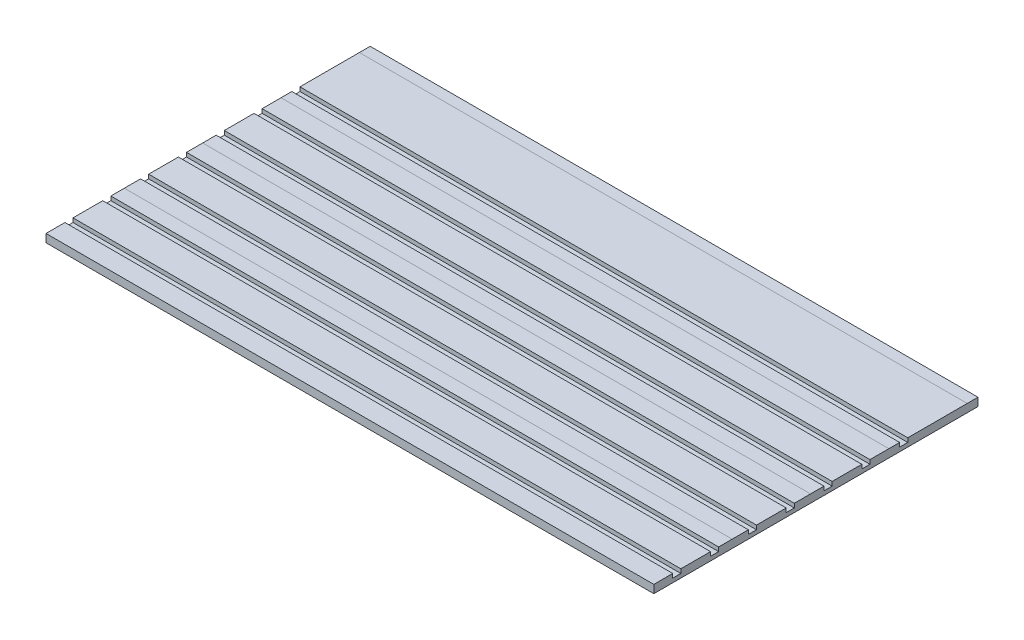
SolidWorks part; units mm, degrees
material "Maple"
ref_plane "Front Plane" through (0, 0, 0) normal (0, 0, 1) x (1, 0, 0)
ref_plane "Top Plane" through (0, 0, 0) normal (0, 1, 0) x (1, 0, 0)
ref_plane "Right Plane" through (0, 0, 0) normal (1, 0, 0) x (0, 0, -1)
sketch "Sketch1" plane through (0, 0, 0) normal (0, 1, 0) x (1, 0, 0)
  line L0 (-714.375, -381) -> (714.375, 381) construction
  line L1 (-714.375, -381) -> (714.375, -381)
  line L2 (-714.375, -381) -> (-714.375, 381)
  line L3 (-714.375, 381) -> (714.375, 381)
  line L4 (714.375, -381) -> (714.375, 381)
  dimension "D1" = 1428.75
  dimension "D2" = 762
extrude "Board" add sketch "Sketch1" along normal blind 19.05
sketch "Sketch4" plane through (-714.375, 0, 0) normal (-1, 0, 0) x (0, 0, 1)
  line L0 (-381, 19.05) -> (-381, 0) construction
  line L1 (-381, 19.05) -> (381, 19.05) construction
  line L2 (355.6, 19.05) -> (355.6, 9.525)
  line L3 (-357.4034, 19.05) -> (-338.3534, 19.05)
  line L4 (-357.4034, 19.05) -> (-357.4034, 9.525)
  line L5 (-357.4034, 9.525) -> (-338.3534, 9.525)
  line L6 (-338.3534, 19.05) -> (-338.3534, 9.525)
  line L7 (355.6, 19.05) -> (336.55, 19.05)
  line L8 (336.55, 19.05) -> (336.55, 9.525)
  line L9 (355.6, 9.525) -> (336.55, 9.525)
  line L11 (152.4, 19.05) -> (171.45, 19.05)
  line L12 (152.4, 19.05) -> (152.4, 9.525)
  line L13 (152.4, 9.525) -> (171.45, 9.525)
  line L14 (171.45, 19.05) -> (171.45, 9.525)
  line L15 (-196.85, 19.05) -> (-215.9, 19.05)
  line L16 (-196.85, 19.05) -> (-196.85, 9.525)
  line L17 (-196.85, 9.525) -> (-215.9, 9.525)
  line L18 (-12.7, 19.05) -> (-12.7, 9.525)
  line L19 (-215.9, 19.05) -> (-215.9, 9.525)
  line L23 (-12.7, 19.05) -> (-31.75, 19.05)
  line L24 (-31.75, 19.05) -> (-31.75, 9.525)
  line L25 (-12.7, 9.525) -> (-31.75, 9.525)
  dimension "D1" = 19.05
  dimension "D2" = 9.525
  dimension "D3" = 717.55
  dimension "D4" = 23.5966
  dimension "D5" = 165.1
  dimension "D6" = 165.1
  dimension "D7" = 165.1
extrude "X- Axis Grooves" [suppressed] cut sketch "Sketch4" against normal up to surface (1428.75 mm away) up to face at (714.375, 9.525, 0)
sketch "Sketch5" plane through (0, 0, 381) normal (0, 0, 1) x (1, 0, 0)
  line L0 (-714.375, 19.05) -> (714.375, 19.05) construction
  line L1 (-695.325, 19.05) -> (-676.275, 19.05)
  line L2 (-695.325, 19.05) -> (-695.325, 9.525)
  line L3 (-695.325, 9.525) -> (-676.275, 9.525)
  line L4 (-676.275, 19.05) -> (-676.275, 9.525)
  line L5 (-714.375, 19.05) -> (-714.375, 0) construction
  line L6 (-346.075, 19.05) -> (-327.025, 19.05)
  line L7 (-346.075, 19.05) -> (-346.075, 9.525)
  line L8 (-346.075, 9.525) -> (-327.025, 9.525)
  line L9 (-327.025, 19.05) -> (-327.025, 9.525)
  line L22 (568.325, 19.05) -> (587.375, 19.05)
  line L23 (568.325, 19.05) -> (568.325, 9.525)
  line L24 (568.325, 9.525) -> (587.375, 9.525)
  line L25 (587.375, 19.05) -> (587.375, 9.525)
  dimension "D1" = 19.05
  dimension "D2" = 19.05
  dimension "D3" = 9.525
  dimension "D4" = 330.2
  dimension "D5" = 1244.6
extrude "Y-Axis Grooves" [suppressed] cut sketch "Sketch5" against normal up to surface (704.85 mm away) up to face at (0, 9.525, -381)
sketch "Sketch6" plane through (0, 19.05, 0) normal (0, 1, 0) x (1, 0, 0)
  line L0 (-598.0647, 61.6513) -> (567.6073, 61.6513) construction
  text T0 "1'x1'\r\n" font "Century Gothic" height 76.2
extrude "\"1\"" [suppressed] cut sketch "Sketch6" against normal blind 1.27
sketch "Sketch7" plane through (0, 19.05, 0) normal (0, 1, 0) x (1, 0, 0)
  line L0 (-70.4936, -248.9336) -> (1439.7947, -248.9336) construction
  text T0 "2'x4'\r\n" font "Century Gothic" height 152.4
extrude "\"2'x4'\"" [suppressed] cut sketch "Sketch7" against normal blind 1.27
sketch "Sketch8" [suppressed] plane through (-714.375, 0, 0) normal (-1, 0, 0) x (0, 0, 1)
  line L1 (-389.1534, 19.05) -> (-370.1034, 19.05)
  line L2 (-389.1534, 19.05) -> (-389.1534, 9.525)
  line L3 (-389.1534, 9.525) -> (-370.1034, 9.525)
  line L4 (-370.1034, 19.05) -> (-370.1034, 9.525)
extrude "Boss-Extrude1" [suppressed] add sketch "Sketch8" against normal up to surface (1428.75 mm away) up to face at (714.375, 9.525, 0)
sketch "Sketch9" plane through (-714.375, 0, 0) normal (-1, 0, 0) x (0, 0, 1)
  line L0 (-381, 19.05) -> (381, 19.05) construction
  line L1 (317.5, 19.05) -> (336.55, 19.05)
  line L2 (317.5, 19.05) -> (317.5, 9.525)
  line L3 (317.5, 9.525) -> (336.55, 9.525)
  line L4 (336.55, 19.05) -> (336.55, 9.525)
  line L5 (381, 19.05) -> (381, 0) construction
  dimension "D1" = 19.05
  dimension "D2" = 9.525
  dimension "D3" = 44.45
extrude "Cut-Extrude1" cut sketch "Sketch9" against normal through all
pattern_linear "LPattern1" count 7 spacing 88.9 along (0, 0, -1) of "Cut-Extrude1"
sketch "Sketch10" plane through (0, 19.05, 0) normal (0, 1, 0) x (1, 0, 0)
  line L0 (-714.375, 355.6) -> (714.375, 355.6)
  line L1 (-714.375, 196.85) -> (-714.375, 127) construction
  line L2 (714.375, 127) -> (714.375, 196.85) construction
  line L3 (-714.375, 171.45) -> (714.375, 171.45)
  line L4 (-714.375, 19.05) -> (-714.375, -50.8) construction
  line L5 (714.375, -50.8) -> (714.375, 19.05) construction
  line L6 (-714.375, -12.7) -> (714.375, -12.7)
  line L7 (-714.375, -69.85) -> (-714.375, -139.7) construction
  line L8 (714.375, -139.7) -> (714.375, -69.85) construction
  line L9 (-714.375, -196.85) -> (714.375, -196.85)
  line L10 (-714.375, -158.75) -> (-714.375, -228.6) construction
  line L11 (714.375, -228.6) -> (714.375, -158.75) construction
  line L12 (-714.375, -381) -> (714.375, -381) construction
  dimension "D1" = 184.15
  dimension "D2" = 184.15
  dimension "D3" = 184.15
  dimension "D4" = 184.15
split line "Split Line1"
